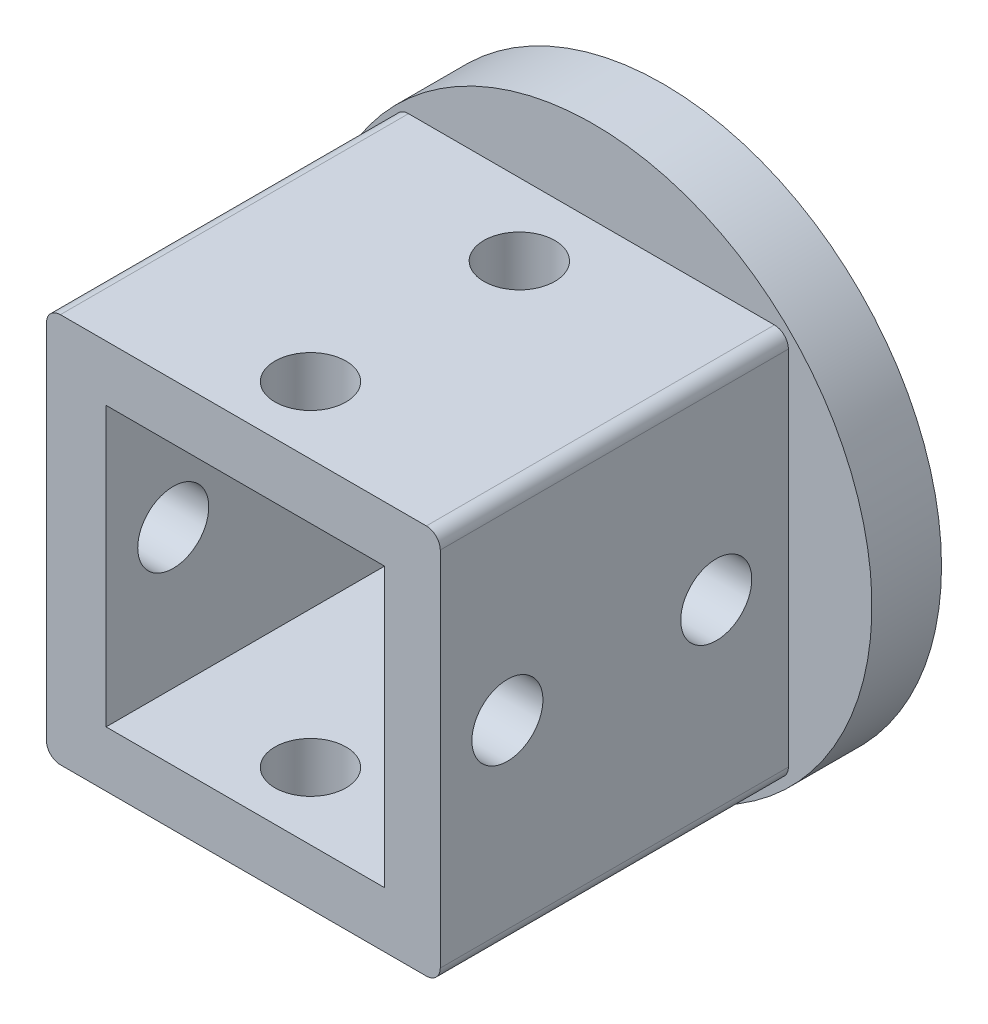
SolidWorks part; units mm, degrees
ref_plane "前视基准面" through (0, 0, 0) normal (0, 0, 1) x (1, 0, 0)
ref_plane "上视基准面" through (0, 0, 0) normal (0, 1, 0) x (1, 0, 0)
ref_plane "右视基准面" through (0, 0, 0) normal (1, 0, 0) x (0, 0, -1)
sketch "草图1" plane through (0, 0, 0) normal (0, 0, 1) x (1, 0, 0)
  circle A0 centre (0, 0) radius 20
  dimension "D1" = 40
extrude "凸台-拉伸1" add sketch "草图1" along normal blind 5
sketch "草图2" plane through (0, 0, 5) normal (0, 0, 1) x (1, 0, 0)
  line L1 (4.95, -4.95) -> (-4.95, -4.95) construction
  line L2 (4.95, -4.95) -> (4.95, 4.95) construction
  line L3 (4.95, 4.95) -> (-4.95, 4.95) construction
  line L4 (-4.95, -4.95) -> (-4.95, 4.95) construction
  line L5 (4.95, -4.95) -> (-4.95, 4.95) construction
  line L6 (4.95, 4.95) -> (-4.95, -4.95) construction
  circle A0 centre (-4.95, 4.95) radius 1.5
  circle A1 centre (4.95, 4.95) radius 1.5
  circle A2 centre (-4.95, -4.95) radius 1.5
  circle A3 centre (4.95, -4.95) radius 1.5
  point P0 (0, 0)
  dimension "D3" = 3
  dimension "D4" = 3
  dimension "D5" = 3
  dimension "D6" = 3
  dimension "D1" = 9.9
  dimension "D2" = 9.9
extrude "切除-拉伸1" cut sketch "草图2" against normal blind 5
sketch "草图4" plane through (0, 0, 5) normal (0, 0, 1) x (1, 0, 0)
  line L1 (10, -10) -> (-10, -10)
  line L2 (10, -10) -> (10, 10)
  line L3 (10, 10) -> (-10, 10)
  line L4 (-10, -10) -> (-10, 10)
  line L5 (10, -10) -> (-10, 10) construction
  line L6 (10, 10) -> (-10, -10) construction
  line L7 (-10, 10) -> (10, 10)
  line L8 (-10, 10) -> (-10, 14)
  line L9 (-10, 14) -> (10, 14)
  line L10 (10, 10) -> (10, 14)
  line L11 (-10, -10) -> (10, -10)
  line L12 (-10, -10) -> (-10, -14)
  line L13 (-10, -14) -> (10, -14)
  line L14 (10, -10) -> (10, -14)
  line L15 (-10, -14) -> (-14.2829, -14)
  line L16 (-10, -14) -> (-10, 14)
  line L17 (-10, 14) -> (-14.2829, 14)
  line L18 (-14.2829, -14) -> (-14.2829, 14)
  line L19 (10, -14) -> (14, -14)
  line L20 (10, -14) -> (10, 14)
  line L21 (10, 14) -> (14, 14)
  line L22 (14, -14) -> (14, 14)
  circle A0 centre (0, 0) radius 20 construction
  point P0 (0, 0)
  dimension "D1" = 20
  dimension "D2" = 20
  dimension "D3" = 20
  dimension "D4" = 4
  dimension "D5" = 4
  dimension "D6" = 4
extrude "凸台-拉伸3" add sketch "草图4" along normal blind 25 contours L18 L15 L12 L4 L8 L17 | L3 L10 L9 L8 | L14 L1 L12 L13 | L19 L22 L21 L10 L2 L14 region at (0, -12, 5) region at (12, 0, 5) region at (-12.1414, 0, 5) region at (0, 12, 5)
sketch "草图5" plane through (-14.2829, 0, 0) normal (-1, 0, 0) x (0, 0, 1)
  line L0 (30, 0) -> (0, 0) construction
  line L1 (30, -14) -> (30, 14) construction
  circle A0 centre (10.1786, 0) radius 2.55
  circle A1 centre (25.1786, 0) radius 2.55
  circle A2 centre (40.1786, 0) radius 2.55
  dimension "D1" = 3
  dimension "D2" = 5.1
extrude "切除-拉伸2" cut sketch "草图5" against normal through all
sketch "草图6" plane through (0, 14, 0) normal (0, 1, 0) x (1, 0, 0)
  line L0 (-0.1414, -5) -> (-0.1414, -10.18) construction
  line L1 (14, -5) -> (-14.2829, -5) construction
  circle A0 centre (-0.1414, -10.18) radius 2.55
  circle A1 centre (-0.1414, -25.18) radius 2.55
  circle A2 centre (-0.1414, -40.18) radius 2.55
  dimension "D1" = 5.18
  dimension "D2" = 5.1
  dimension "D3" = 3
extrude "切除-拉伸3" cut sketch "草图6" against normal through all
fillet "圆角2" radius 1 4 edges at (-14.2829, -14, 17.5) (14, -14, 17.5) (-14.2829, 14, 17.5) (14, 14, 17.5)
